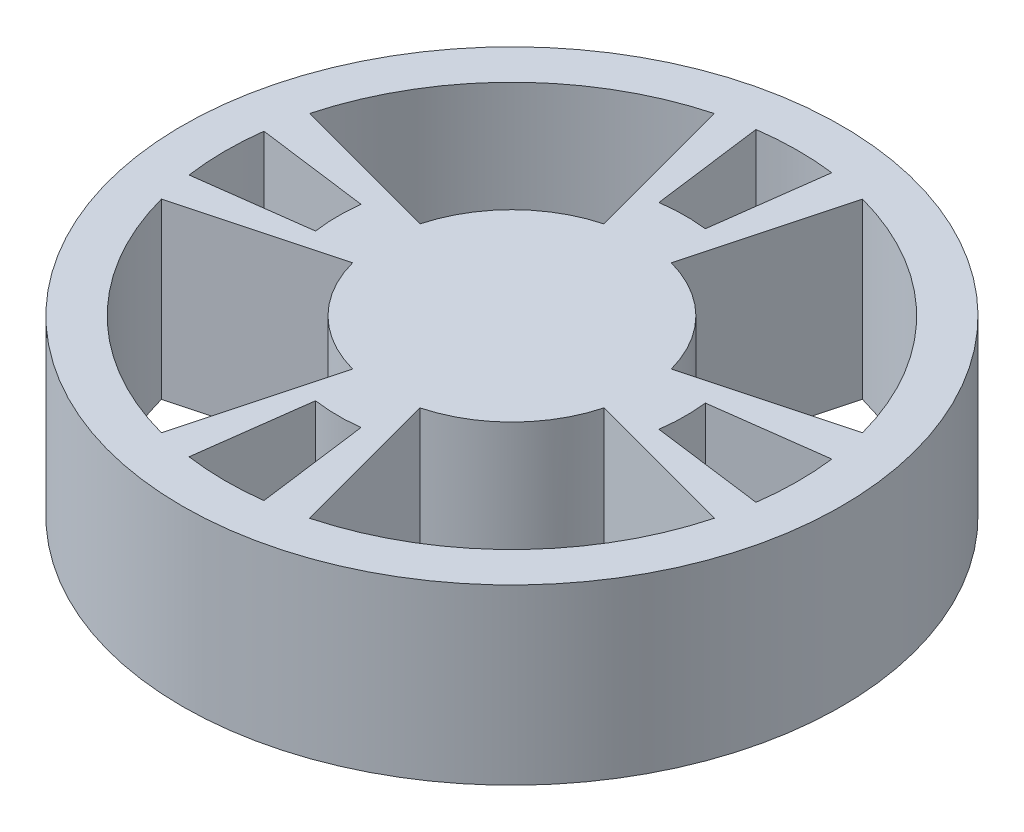
SolidWorks part; units mm, degrees
ref_plane "Front Plane" through (0, 0, 0) normal (0, 0, 1) x (1, 0, 0)
ref_plane "Top Plane" through (0, 0, 0) normal (0, 1, 0) x (1, 0, 0)
ref_plane "Right Plane" through (0, 0, 0) normal (1, 0, 0) x (0, 0, -1)
sketch "Sketch1" plane through (0, 0, 0) normal (0, 1, 0) x (1, 0, 0)
  circle A0 centre (0, 0) radius 9.525
  dimension "D1" = 19.05
extrude "Boss-Extrude1" add sketch "Sketch1" along normal blind 2.54
sketch "Sketch3" plane through (0, 2.54, 0) normal (0, 1, 0) x (1, 0, 0)
  line L0 (0, 0) -> (24.13, 0) construction
  line L1 (0, 0) -> (0, 24.13) construction
  line L2 (0, 0) -> (23.3078, 6.2453) construction
  line L3 (-2.4653, 9.2004) -> (-5.4236, 20.241)
  line L4 (9.2004, 2.4653) -> (20.241, 5.4236)
  line L5 (-9.2004, 2.4653) -> (-20.241, 5.4236)
  line L6 (0, 0) -> (17.0625, 17.0625) construction
  line L8 (2.4653, 9.2004) -> (5.4236, 20.241)
  line L9 (9.2004, -2.4653) -> (20.241, -5.4236)
  line L10 (2.4653, -9.2004) -> (5.4236, -20.241)
  line L11 (-9.2004, -2.4653) -> (-20.241, -5.4236)
  line L12 (-2.4653, -9.2004) -> (-5.4236, -20.241)
  circle A0 centre (0, 0) radius 24.13
  circle A2 centre (0, 0) radius 20.955 construction
  circle A3 centre (0, 0) radius 9.525 construction
  arc A4 (-9.2004, 2.4653) -> (-2.4653, 9.2004) centre (0, 0) cw
  arc A5 (9.2004, 2.4653) -> (2.4653, 9.2004) centre (0, 0) ccw
  arc A8 (20.241, 5.4236) -> (5.4236, 20.241) centre (0, 0) ccw
  arc A9 (-20.241, 5.4236) -> (-5.4236, 20.241) centre (0, 0) cw
  arc A10 (9.2004, -2.4653) -> (2.4653, -9.2004) centre (0, 0) cw
  arc A11 (20.241, -5.4236) -> (5.4236, -20.241) centre (0, 0) cw
  arc A12 (-20.241, -5.4236) -> (-5.4236, -20.241) centre (0, 0) ccw
  arc A13 (-9.2004, -2.4653) -> (-2.4653, -9.2004) centre (0, 0) ccw
  dimension "D1" = 48.26
  dimension "D2" = 15
  dimension "D4" = 3.175
  dimension "D3" = 45
extrude "Boss-Extrude2" add sketch "Sketch3" along normal blind 12.7
sketch "Sketch4" plane through (0, 15.24, 0) normal (0, 1, 0) x (1, 0, 0)
  line L0 (0, 0) -> (24.13, 0) construction
  line L1 (0, 0) -> (0, 24.13) construction
  line L2 (12.6046, 1.5541) -> (20.7891, 2.6316)
  line L5 (12.5705, -1.8088) -> (20.7553, -2.8863)
  line L6 (-12.6046, 1.5541) -> (-20.7891, 2.6316)
  line L7 (-12.5705, -1.8088) -> (-20.7553, -2.8863)
  line L8 (0, 0) -> (17.0625, 17.0625) construction
  line L9 (1.5541, 12.6046) -> (2.6316, 20.7891)
  line L10 (-1.8088, 12.5705) -> (-2.8863, 20.7553)
  line L11 (-1.8088, -12.5705) -> (-2.8863, -20.7553)
  line L12 (1.5541, -12.6046) -> (2.6316, -20.7891)
  circle A2 centre (0, 0) radius 12.7 construction
  arc A3 (-2.4653, 9.2004) -> (-9.2004, 2.4653) centre (0, 0) ccw construction
  circle A4 centre (0, 0) radius 20.955 construction
  arc A5 (12.5705, -1.8088) -> (12.6046, 1.5541) centre (0, 0) ccw
  arc A6 (-5.4236, 20.241) -> (-20.241, 5.4236) centre (0, 0) ccw construction
  circle A7 centre (0, 0) radius 24.13 construction
  arc A8 (20.7553, -2.8863) -> (20.7891, 2.6316) centre (0, 0) ccw
  arc A9 (-12.5705, -1.8088) -> (-12.6046, 1.5541) centre (0, 0) cw
  arc A10 (-20.7553, -2.8863) -> (-20.7891, 2.6316) centre (0, 0) cw
  arc A11 (-1.8088, 12.5705) -> (1.5541, 12.6046) centre (0, 0) cw
  arc A12 (-2.8863, 20.7553) -> (2.6316, 20.7891) centre (0, 0) cw
  arc A13 (-2.8863, -20.7553) -> (2.6316, -20.7891) centre (0, 0) ccw
  arc A14 (-1.8088, -12.5705) -> (1.5541, -12.6046) centre (0, 0) ccw
  dimension "D1" = 3.175
  dimension "D2" = 0
  dimension "D3" = 7.5
  dimension "D4" = 7.5
  dimension "D5" = 45
extrude "Cut-Extrude2" cut sketch "Sketch4" against normal through all
sketch "Sketch2" plane through (0, 0, 0) normal (0, 1, 0) x (1, 0, 0)
  line L1 (-4.5529, 1.8859) -> (-1.8859, 4.5529)
  line L2 (-2.667, 2.667) -> (2.667, -2.667) construction
  line L3 (0, 2.667) -> (-1.8859, 4.5529)
  line L4 (1.8859, 4.5529) -> (4.5529, 1.8859)
  line L5 (0, 2.667) -> (1.8859, 4.5529)
  line L6 (0, -2.667) -> (1.8859, -4.5529)
  line L7 (-4.5529, -1.8859) -> (-1.8859, -4.5529)
  line L8 (-2.667, 0) -> (-4.5529, 1.8859)
  line L9 (1.8859, -4.5529) -> (4.5529, -1.8859)
  line L10 (-2.667, -2.667) -> (2.667, -2.667) construction
  line L11 (-2.667, 0) -> (-4.5529, -1.8859)
  line L12 (2.667, 0) -> (4.5529, 1.8859)
  line L13 (-2.667, 2.667) -> (2.667, 2.667) construction
  line L14 (2.667, 0) -> (4.5529, -1.8859)
  line L15 (2.667, -2.667) -> (2.667, 2.667) construction
  line L16 (-2.667, -2.667) -> (-2.667, 2.667) construction
  line L17 (0, -2.667) -> (-1.8859, -4.5529)
  line L18 (-2.667, -2.667) -> (2.667, 2.667) construction
  point P23 (-2.667, 0)
  dimension "D1" = 3.7717
  dimension "D2" = 2.667
  dimension "D3" = 2.667
  dimension "D4" = 3.7717
  dimension "D5" = 2.667
  dimension "D6" = 2.667
  dimension "D7" = 3.7717
  dimension "D8" = 2.667
  dimension "D9" = 2.667
  dimension "D10" = 3.7717
  dimension "D11" = 2.667
  dimension "D12" = 2.667
  dimension "D13" = 5.334
  dimension "D14" = 5.334
  dimension "D15" = 3.7717
extrude "Cut-Extrude3" cut sketch "Sketch2" along normal blind 8.4667
